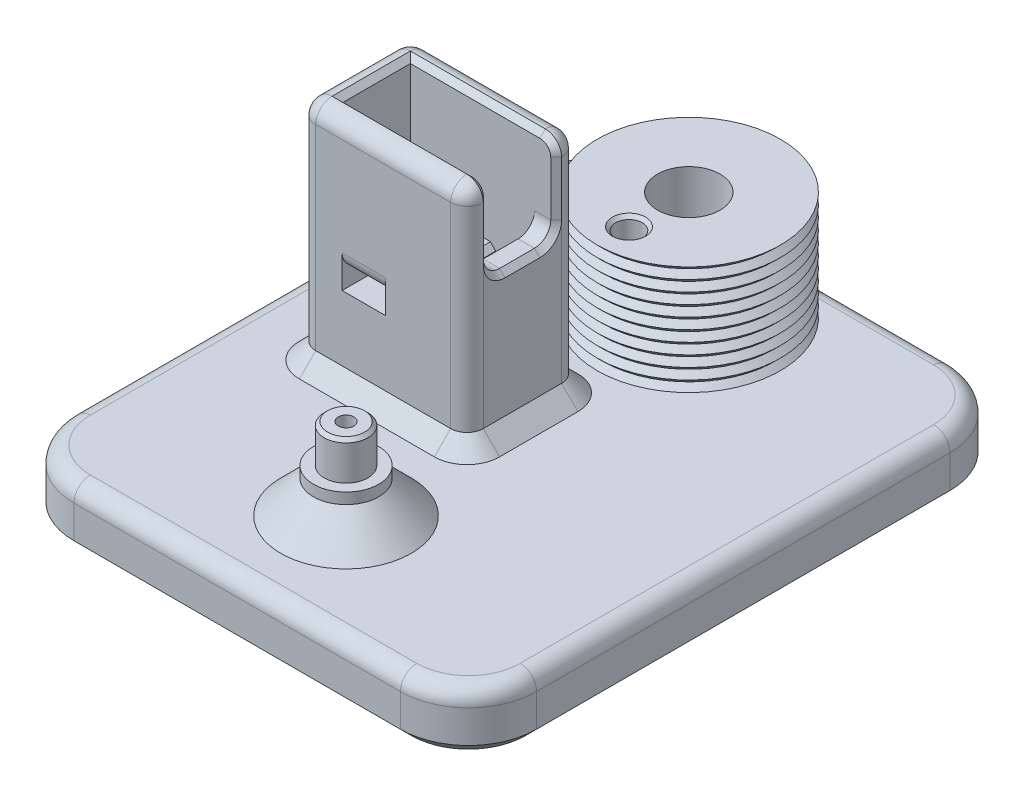
SolidWorks part; units mm, degrees
ref_plane "Front Plane" through (0, 0, 0) normal (0, 0, 1) x (1, 0, 0)
ref_plane "Top Plane" through (0, 0, 0) normal (0, 1, 0) x (1, 0, 0)
ref_plane "Right Plane" through (0, 0, 0) normal (1, 0, 0) x (0, 0, -1)
sketch "Sketch1" plane through (0, 0, 0) normal (0, 1, 0) x (1, 0, 0)
  line L3 (-30, 0) -> (30, 0)
  line L4 (42.5, 12.5) -> (42.5, 88.5)
  line L5 (-42.5, 88.5) -> (-42.5, 12.5)
  line L6 (-30, 101) -> (30, 101)
  line L7 (0, 101) -> (0, 0) construction
  arc A0 (30, 0) -> (42.5, 12.5) centre (30, 12.5) ccw
  arc A2 (-42.5, 12.5) -> (-30, 0) centre (-30, 12.5) ccw
  circle A3 centre (-30, 12.5) radius 6.5 construction
  arc A4 (-30, 101) -> (-42.5, 88.5) centre (-30, 88.5) ccw
  arc A5 (42.5, 88.5) -> (30, 101) centre (30, 88.5) ccw
  point P4 (0, 0)
  dimension "D1" = 13
  dimension "D2" = 6
  dimension "D5" = 60
  dimension "50" = 76
  dimension "D4" = 60
extrude "Boss-Extrude1" add sketch "Sketch1" along normal blind 11
sketch "Sketch2" plane through (0, 0, 0) normal (0, -1, 0) x (1, 0, 0)
  circle A0 centre (-30, -12.5) radius 6.65
  circle A1 centre (30, -12.5) radius 6.65
  circle A2 centre (-30, -88.5) radius 6.65
  circle A3 centre (30, -88.5) radius 6.65
  dimension "D1" = 13.3
extrude "Cut-Extrude1" cut sketch "Sketch2" against normal blind 9
sketch "Sketch3" plane through (0, 0, 0) normal (0, -1, 0) x (1, 0, 0)
  circle A0 centre (-30, -12.5) radius 8.5
  circle A1 centre (30, -12.5) radius 8.5
  circle A2 centre (-30, -88.5) radius 8.5
  circle A3 centre (30, -88.5) radius 8.5
  dimension "D1" = 17
extrude "Cut-Extrude2" cut sketch "Sketch3" against normal blind 2
sketch "Sketch4" plane through (0, 0, 0) normal (0, -1, 0) x (1, 0, 0)
  line L0 (0, -101) -> (0, -83) construction
  line L1 (30, -101) -> (-30, -101) construction
  circle A0 centre (0, -83) radius 5.75
  circle A1 centre (-30, -88.5) radius 8.5 construction
  dimension "D1" = 11.5
  dimension "D2" = 18
  dimension "D3" = 16.25
extrude "Cut-Extrude3" cut sketch "Sketch4" against normal up to surface (11 mm away) up to face at (0, 11, -50.5)
sketch "Sketch5" plane through (0, 11, 0) normal (0, 1, 0) x (1, 0, 0)
  circle A1 centre (0, 72) radius 2.45
  circle A2 centre (0, 72) radius 2.6 construction
  dimension "D1" = 4.9
extrude "Cut-Extrude4" cut sketch "Sketch5" against normal blind 5
sketch "Sketch10" plane through (0, 11, 0) normal (0, 1, 0) x (1, 0, 0)
  circle A0 centre (0, 83) radius 15.85
  circle A1 centre (0, 72) radius 2.45 construction
  circle A2 centre (0, 83) radius 5.75 construction
  circle A3 centre (0, 72) radius 2.45
  circle A4 centre (0, 83) radius 5.75
  dimension "D1" = 2.4
extrude "Boss-Extrude5" add sketch "Sketch10" along normal blind 20
sketch "Sketch11" plane through (0, 11, 0) normal (0, 1, 0) x (1, 0, 0)
  line L0 (0, 20) -> (0, 0) construction
  circle A0 centre (0, 20) radius 4
  dimension "D1" = 8
  dimension "D2" = 20
extrude "Boss-Extrude6" add sketch "Sketch11" along normal blind 15
sketch "Sketch12" plane through (0, 11, 0) normal (0, 1, 0) x (1, 0, 0)
  line L0 (-6.65, 53) -> (-9.35, 53) construction
  line L1 (6.7, 48.375) -> (6.7, 52.975) construction
  line L2 (-2.25, 56.875) -> (-2.25, 44.475)
  line L3 (-2.25, 56.875) -> (-25.05, 56.875)
  line L4 (-2.25, 44.475) -> (-25.05, 44.475)
  line L5 (-25.05, 56.875) -> (-25.05, 44.475)
  line L6 (-2.25, 50.675) -> (6.7, 50.675) construction
  line L7 (-9.35, 56.875) -> (-9.35, 44.475)
  line L8 (-6.65, 44.475) -> (-6.65, 56.875)
  line L9 (1.75, 60.875) -> (-29.05, 60.875)
  line L10 (-29.05, 60.875) -> (-29.05, 40.475)
  line L11 (1.75, 40.475) -> (-29.05, 40.475)
  line L12 (1.75, 60.875) -> (1.75, 40.475)
  line L13 (6.7, 48.375) -> (6.7, 52.975) construction
  line L14 (-9.25, 51.225) -> (-6.75, 51.225) construction
  line L15 (-9.25, 51.225) -> (-6.75, 51.225) construction
  line L16 (-8, 53) -> (-8, 51.225) construction
  line L17 (-9.25, 51.225) -> (-6.75, 51.225) construction
  point P23 (-8, 51.225)
  line M12 (-42.5, 88.5) -> (-42.5, 12.5)
  dimension "D2" = 2.7
  dimension "D3" = 12.4
  dimension "D4" = 22.8
  dimension "D5" = 4.4
  dimension "D6" = 4
extrude "Boss-Extrude7" add sketch "Sketch12" along normal blind 20 contours L7 L3 L5 L4 | L8 L4 L2 L3 region at (-4.45, 11, -50.675) region at (-17.2, 11, -50.675)
extrude "Boss-Extrude8" add sketch "Sketch12<5>" along normal blind 42 contours L12 L9 L10 L11 L5 L3 L2 L4 M12 | L9 L10 M12 region at (1.3806, 11, -50.675)
sketch "Sketch12<5>" plane through (0, 11, 0) normal (0, 1, 0) x (1, 0, 0) same geometry as "Sketch12"
extrude "Boss-Extrude9" add sketch "Sketch12<6>" along normal blind 15 contours L4 L8 L3 L7 region at (-8, 11, -50.675)
sketch "Sketch12<6>" plane through (0, 11, 0) normal (0, 1, 0) x (1, 0, 0) same geometry as "Sketch12"
sketch "Sketch14" plane through (1.75, 0, 0) normal (1, 0, 0) x (0, 0, -1)
  line L0 (44.475, 37) -> (56.875, 37)
  line L4 (44.475, 31) -> (56.875, 31)
  line L5 (44.475, 53) -> (44.475, 31)
  line L6 (56.875, 53) -> (44.475, 53)
  line L7 (56.875, 31) -> (56.875, 53)
  line L10 (56.875, 53) -> (44.475, 53)
  line L13 (56.875, 37) -> (56.875, 53)
  line L14 (44.475, 53) -> (44.475, 37)
  dimension "D2" = 16
  dimension "D1" = 0
extrude "Cut-Extrude6" cut sketch "Sketch14" against normal up to surface (4 mm away) up to face at (-2.25, 42, -50.675)
sketch "Sketch13" plane through (0, 0, -40.475) normal (0, 0, 1) x (1, 0, 0)
  line L0 (-9.35, 31) -> (-25.05, 31) construction
  line L1 (-21.2, 29) -> (-13.2, 29)
  line L2 (-21.2, 29) -> (-21.2, 26)
  line L3 (-21.2, 26) -> (-13.2, 26)
  line L4 (-13.2, 29) -> (-13.2, 26)
  line L5 (-9.35, 31) -> (-25.05, 31) construction
  line L6 (-17.2, 29) -> (-17.2, 31) construction
  dimension "D1" = 8
  dimension "D2" = 3
  dimension "D3" = 2
extrude "Cut-Extrude5" cut sketch "Sketch13" against normal up to surface (20.4 mm away) up to face at (-13.65, 32, -60.875)
sketch "Sketch17" plane through (0, 0, 0) normal (1, 0, 0) x (0, 0, -1)
  line L5 (98.85, 31) -> (99.85, 31)
  line L6 (98.85, 31) -> (98.85, 29)
  line L11 (83, 31) -> (83, 11) construction
  line L12 (88.75, 31) -> (77.25, 31) construction
  line L13 (12.5, 11) -> (88.5, 11) construction
  line L15 (98.85, 11) -> (98.85, 31) construction
  line L17 (98.85, 29) -> (98.85, 31)
  line L19 (99.85, 31) -> (98.85, 30)
  line L20 (98.85, 11) -> (98.85, 31) construction
  line L21 (98.85, 30) -> (99.85, 29)
  line L22 (99.85, 29) -> (98.85, 29)
  point P2 (100.9539, 28.0327)
  dimension "D1" = 1
revolve "Revolve1" add sketch "Sketch17" angle 360 about L11 region at (0, 29.3333, -99.1833) region at (0, 30.6667, -99.1833)
pattern_linear "LPattern1" count 10 spacing 2 along (0, -1, 0) of "Revolve1"
sketch "Sketch18" plane through (0, 11, 0) normal (0, 1, 0) x (1, 0, 0)
  circle A0 centre (0, 20) radius 6
  dimension "D1" = 12
extrude "Boss-Extrude10" add sketch "Sketch18" along normal blind 8
fillet "Fillet1" radius 3 13 edges at (-17.2, 29, -40.475) (-17.2, 29, -60.875) (-13.65, 53, -60.875) (-13.65, 53, -40.475) (-0.25, 37, -44.475) (-0.25, 37, -56.875) (1.75, 32, -60.875) (1.75, 32, -40.475) (-29.05, 32, -60.875) (-29.05, 32, -40.475) (1.75, 53, -42.475) (1.75, 53, -58.875) (-29.05, 53, -50.675)
chamfer "Chamfer4" distance 3 angle 45 8 edges at (0.8713, 11, -59.9963) (-28.1713, 11, -59.9963) (-29.05, 11, -50.675) (0.8713, 11, -41.3536) (-28.1713, 11, -41.3536) (-13.65, 11, -40.475) (1.75, 11, -50.675) (-13.65, 11, -60.875)
chamfer "Chamfer5" distance 6 angle 45 1 edges at (0, 11, -14)
chamfer "Chamfer1" distance 1 angle 45 12 edges at (-13.15, 53, -44.475) (0.8713, 52.1213, -44.475) (1.75, 45, -44.475) (1.75, 37.8787, -45.3536) (1.75, 37, -50.675) (1.75, 37.8787, -55.9963) (1.75, 45, -56.875) (0.8713, 52.1213, -56.875) (-13.15, 53, -56.875) (-6.65, 31, -50.675) (-9.35, 31, -50.675) (-25.05, 53, -50.675)
chamfer "Chamfer2" distance 0.6 angle 45 2 edges at (0, 26, -16) (0, 31, -69.55)
sketch "Sketch19" plane through (0, 26, 0) normal (0, 1, 0) x (1, 0, 0)
  circle A0 centre (0, 20) radius 1.45
  dimension "D1" = 2.9
extrude "Cut-Extrude7" cut sketch "Sketch19" against normal blind 6
fillet "Fillet3" radius 3 8 edges at (42.5, 11, -50.5) (38.8388, 11, -3.6612) (0, 11, 0) (-38.8388, 11, -3.6612) (-42.5, 11, -50.5) (-38.8388, 11, -97.3388) (0, 11, -101) (38.8388, 11, -97.3388)
chamfer "Chamfer3" distance 2 angle 45 8 edges at (-38.8388, 0, -3.6612) (0, 0, 0) (-42.5, 0, -50.5) (38.8388, 0, -3.6612) (42.5, 0, -50.5) (-38.8388, 0, -97.3388) (0, 0, -101) (38.8388, 0, -97.3388)
